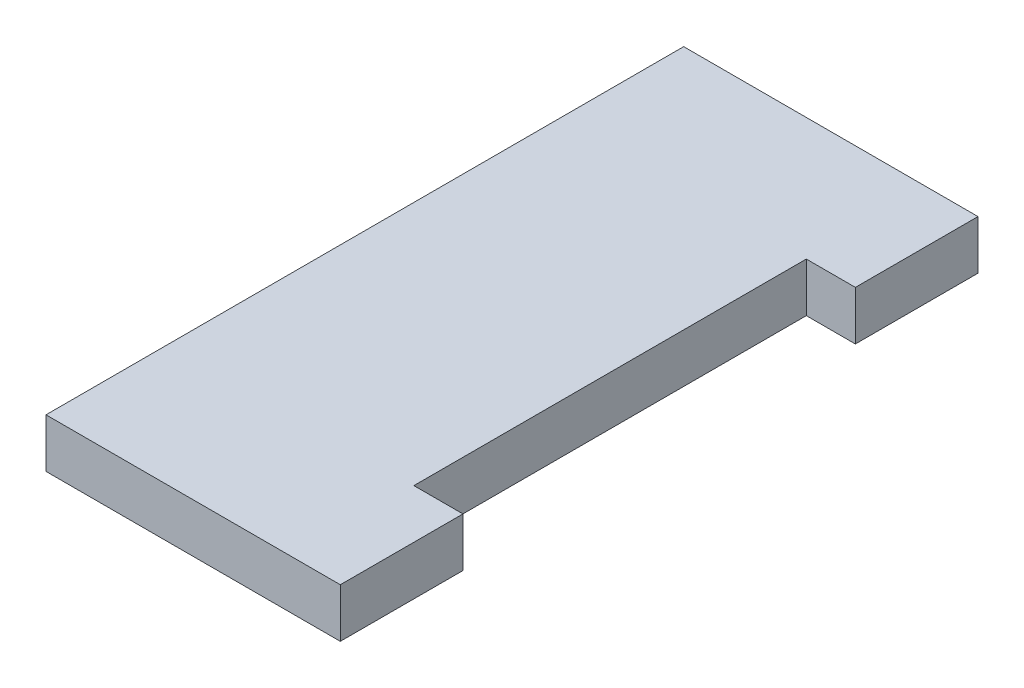
SolidWorks part; units mm, degrees
ref_plane "Front" through (0, 0, 0) normal (0, 0, 1) x (1, 0, 0)
ref_plane "Top" through (0, 0, 0) normal (0, 1, 0) x (1, 0, 0)
ref_plane "Right" through (0, 0, 0) normal (1, 0, 0) x (0, 0, -1)
sketch "Skizze1" plane through (0, 0, 0) normal (0, 1, 0) x (1, 0, 0)
  line L1 (0, 0) -> (120, 0)
  line L2 (0, 0) -> (0, 65)
  line L3 (0, 65) -> (120, 65)
  line L4 (120, 0) -> (120, 65)
  dimension "D1" = 65
  dimension "D2" = 120
extrude "Aufsatz-Linear austragen1" add sketch "Skizze1" along normal blind 5
sketch "Skizze2" plane through (0, 5, 0) normal (0, 1, 0) x (1, 0, 0)
  line L0 (120, 32.5) -> (60, 32.5) construction
  line L1 (120, 0) -> (120, 65) construction
  line L2 (60, 32.5) -> (60, 0) construction
  line L3 (0, 0) -> (120, 0) construction
  line L4 (120, 52.5) -> (120, 12.5)
  line L5 (120, 12.5) -> (115, 12.5)
  line L6 (115, 12.5) -> (115, 52.5)
  line L7 (120, 52.5) -> (115, 52.5)
  line L8 (0, 52.5) -> (5, 52.5)
  line L9 (5, 12.5) -> (5, 52.5)
  line L10 (0, 12.5) -> (5, 12.5)
  line L11 (0, 52.5) -> (0, 12.5)
  point P11 (115, 32.5)
  point P16 (5, 32.5)
  dimension "D1" = 5
  dimension "D2" = 40
extrude "Schnitt-Linear austragen1" cut sketch "Skizze2" against normal through all
sketch "Skizze3" plane through (0, 5, 0) normal (0, 1, 0) x (1, 0, 0)
  line L0 (0, 0) -> (120, 0) construction
  line L1 (90, 0) -> (0, 0)
  line L2 (90, 0) -> (90, 65)
  line L3 (90, 65) -> (0, 65)
  line L4 (0, 0) -> (0, 65)
  line L5 (120, 0) -> (120, 12.5) construction
  dimension "D1" = 30
extrude "Schnitt-Linear austragen2" cut sketch "Skizze3" against normal through all
